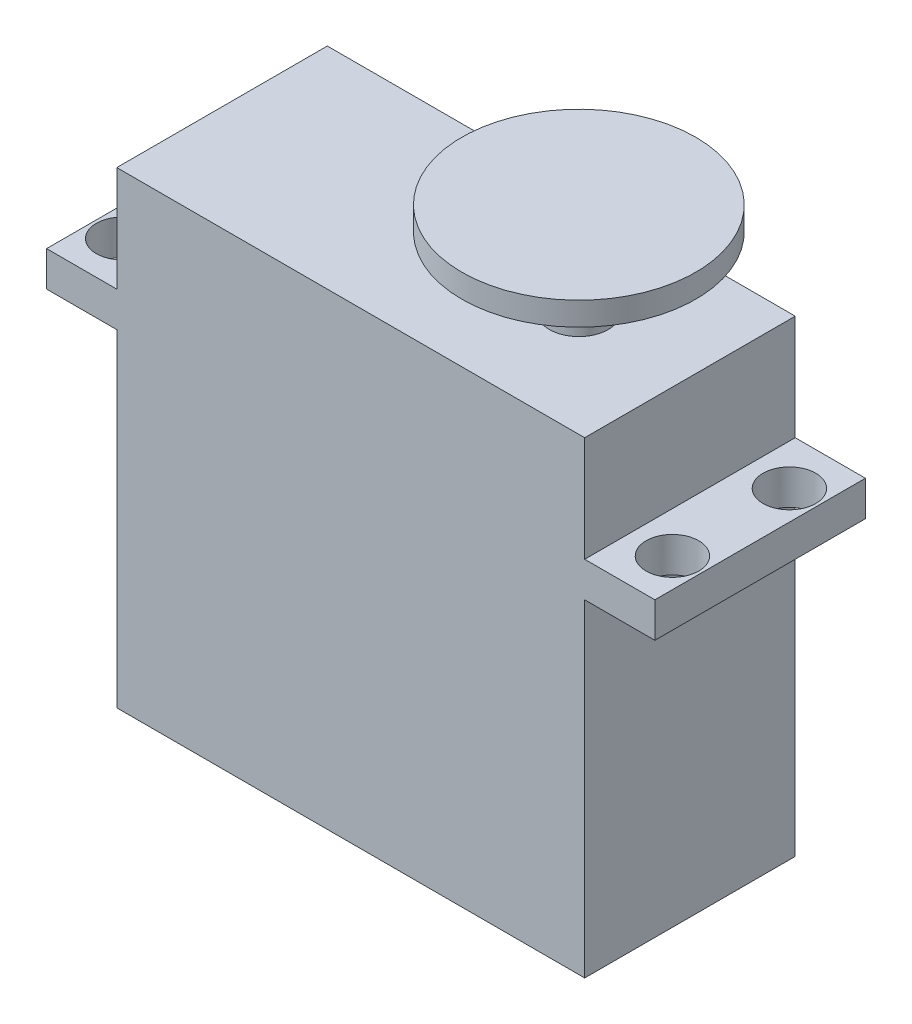
SolidWorks part; units mm, degrees
ref_plane "Front Plane" through (0, 0, 0) normal (0, 0, 1) x (1, 0, 0)
ref_plane "Top Plane" through (0, 0, 0) normal (0, 1, 0) x (1, 0, 0)
ref_plane "Right Plane" through (0, 0, 0) normal (1, 0, 0) x (0, 0, -1)
sketch "Sketch1" plane through (0, 0, 0) normal (0, 1, 0) x (1, 0, 0)
  line L1 (0, 0) -> (40, 0)
  line L2 (0, 0) -> (0, 18)
  line L3 (0, 18) -> (40, 18)
  line L4 (40, 0) -> (40, 18)
  dimension "D1" = 40
  dimension "D2" = 18
extrude "Boss-Extrude1" add sketch "Sketch1" along normal blind 40
ref_plane "Plane1" through (0, 28, 0) normal (0, -1, 0) x (-1, 0, 0)
sketch "Sketch2" plane through (0, 28, 0) normal (0, -1, 0) x (-1, 0, 0)
  line L1 (-40, 0) -> (-46, 0)
  line L2 (-40, 0) -> (-40, 18)
  line L3 (-40, 18) -> (-46, 18)
  line L4 (-46, 0) -> (-46, 18)
  line L5 (0, 18) -> (6, 18)
  line L6 (0, 18) -> (0, 0)
  line L7 (0, 0) -> (6, 0)
  line L8 (0, 0) -> (0, 18)
  line L9 (-40, 0) -> (0, 0)
  line L10 (-40, 18) -> (-40, 0)
  line L11 (0, 18) -> (-40, 18)
  line L12 (0, 0) -> (0, 18)
  line L13 (-40, 0) -> (0, 0)
  line L14 (-40, 18) -> (-40, 0)
  line L15 (0, 18) -> (-40, 18)
  line L16 (6, 18) -> (6, 0)
  point P4 (0, -0.3926)
  dimension "D2" = 6
  dimension "D3" = 6
  dimension "D1" = 0
extrude "Boss-Extrude2" add sketch "Sketch2" against normal blind 3 contours L16 L5 L6 L7 | L4 L1 L2 L3 region at (43, 28, -9) region at (-3, 28, -9)
sketch "Sketch3" plane through (0, 40, 0) normal (0, 1, 0) x (1, 0, 0)
  line L0 (30.5, 18) -> (30.5, 0) construction
  line L1 (40, 18) -> (0, 18) construction
  line L2 (0, 0) -> (40, 0) construction
  line L3 (40, 0) -> (40, 18) construction
  circle A0 centre (30.5, 9) radius 2.5
  point P8 (33.6767, 9)
  dimension "D1" = 9.5
extrude "Boss-Extrude3" add sketch "Sketch3" along normal blind 6
sketch "Sketch4" plane through (0, 46, 0) normal (0, 1, 0) x (1, 0, 0)
  circle A0 centre (30.5, 9) radius 10
extrude "Boss-Extrude4" add sketch "Sketch4" along normal blind 2
sketch "Sketch5" plane through (0, 31, 0) normal (0, 1, 0) x (1, 0, 0)
  line L0 (0, 0) -> (-6, 0) construction
  line L4 (0, 18) -> (0, 0) construction
  line L5 (-3.5, 14) -> (-3.5, 4) construction
  circle A0 centre (-3.5, 14) radius 2.25
  circle A1 centre (-3.5, 4) radius 2.25
  dimension "D1" = 10
  dimension "D4" = 4.5
  dimension "D5" = 4.5
  dimension "D2" = 4
  dimension "D3" = 3.5
ref_plane "Plane2" through (20, 0, 0) normal (-1, 0, 0) x (0, 0, 1)
extrude "Cut-Extrude1" cut sketch "Sketch5" against normal up to next
mirror "Mirror1" about plane through (20, 0, 0) normal (-1, 0, 0) of "Cut-Extrude1"
